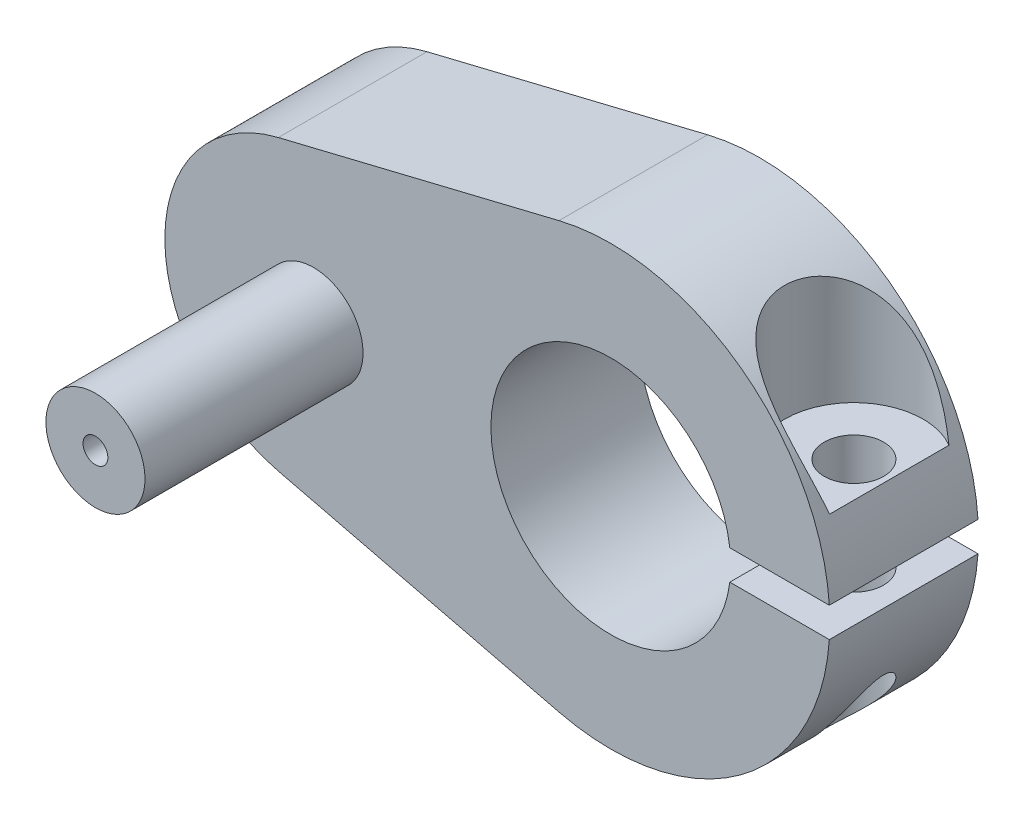
SolidWorks part; units mm, degrees
material "Nylon 6/10"
ref_plane "Front Plane" through (0, 0, 0) normal (0, 0, 1) x (1, 0, 0)
ref_plane "Top Plane" through (0, 0, 0) normal (0, 1, 0) x (1, 0, 0)
ref_plane "Right Plane" through (0, 0, 0) normal (1, 0, 0) x (0, 0, -1)
sketch "Sketch1" plane through (0, 0, 0) normal (0, 0, 1) x (1, 0, 0)
  line L0 (-15, 0) -> (0, 0) construction
  line L1 (-16.775, 7.2869) -> (-2.6152, 10.7361)
  line L2 (-16.775, -7.2869) -> (-2.6152, -10.7361)
  circle A0 centre (0, 0) radius 6.05
  circle A1 centre (-15, 0) radius 2.5 construction
  circle A3 centre (0, 0) radius 1.05
  arc A4 (-16.775, 7.2869) -> (-16.775, -7.2869) centre (-15, 0) ccw
  circle A5 centre (-15, 0) radius 7.5 construction
  arc A8 (-2.6152, -10.7361) -> (-2.6152, 10.7361) centre (0, 0) ccw
  point P6 (0, 0)
  point P10 (-5.7569, 13.5356)
  point P16 (0, 0)
  point P17 (0, 0)
  dimension "D1" = 12.1
  dimension "D3" = 5
  dimension "D4" = 11.05
  dimension "D2" = 15
  dimension "D5" = 5
  dimension "D6" = 5
extrude "Boss-Extrude1" add sketch "Sketch1" against normal blind 7.5 contours L2 A8 L1 A4 A0 region at (-9.6, 8.6212, 0)
sketch "Sketch2" plane through (0, 0, 0) normal (0, 0, 1) x (1, 0, 0)
  circle A0 centre (-15, 0) radius 2.5 construction
  circle A1 centre (-15, 0) radius 2.5
extrude "Boss-Extrude2" add sketch "Sketch2" along normal blind 11
sketch "Sketch3" plane through (0, 0, 0) normal (0, 1, 0) x (1, 0, 0)
  line L0 (11.05, 0) -> (11.05, 7.5) construction
  line L1 (0, 0) -> (22.1, 0)
  line L2 (0, 0) -> (0, 7.5)
  line L3 (0, 7.5) -> (22.1, 7.5)
  line L4 (22.1, 0) -> (22.1, 7.5)
  line L5 (0, 0) -> (22.1, 7.5) construction
  line L6 (0, 7.5) -> (22.1, 0) construction
  line L7 (0, -4.125) -> (0, 4.125) construction
  line L8 (-16.775, 7.5) -> (-2.6152, 7.5) construction
  point P0 (11.05, 3.75)
extrude "Cut-Extrude1" cut sketch "Sketch3" against normal blind 0.75 and the other way blind 0.75
sketch "Sketch4" plane through (0, 0, 11) normal (0, 0, 1) x (1, 0, 0)
  circle A0 centre (-15, 0) radius 0.625
  dimension "D1" = 1.25
extrude "Cut-Extrude2" cut sketch "Sketch4" against normal blind 10
ref_plane "Plane2" through (0, 4, 0) normal (0, 1, 0) x (1, 0, 0)
sketch "Sketch5" plane through (0, 4, 0) normal (0, 1, 0) x (1, 0, 0)
  line L4 (6.0033, 0) -> (11.0245, 7.5) construction
  line L8 (6.0033, 0) -> (11.0245, 0)
  line L9 (11.0245, 0) -> (11.0245, 7.5)
  line L10 (11.0245, 7.5) -> (6.0033, 7.5)
  line L11 (6.0033, 7.5) -> (6.0033, 0)
  line L12 (6.0033, 0) -> (11.0245, 0) construction
  line L13 (11.0245, 0) -> (11.0245, 7.5) construction
  line L14 (11.0245, 7.5) -> (6.0033, 7.5) construction
  line L15 (6.0033, 7.5) -> (6.0033, 0) construction
  circle A0 centre (8.5139, 3.75) radius 3.5
  dimension "D2" = 7
  dimension "D1" = 0
extrude "Cut-Extrude3" cut sketch "Sketch5" along normal through all
sketch "Sketch6" plane through (0, 4, 0) normal (0, 1, 0) x (1, 0, 0)
  circle A0 centre (8.5139, 3.75) radius 1.5
  dimension "D1" = 3
extrude "Cut-Extrude4" cut sketch "Sketch6" against normal through all
